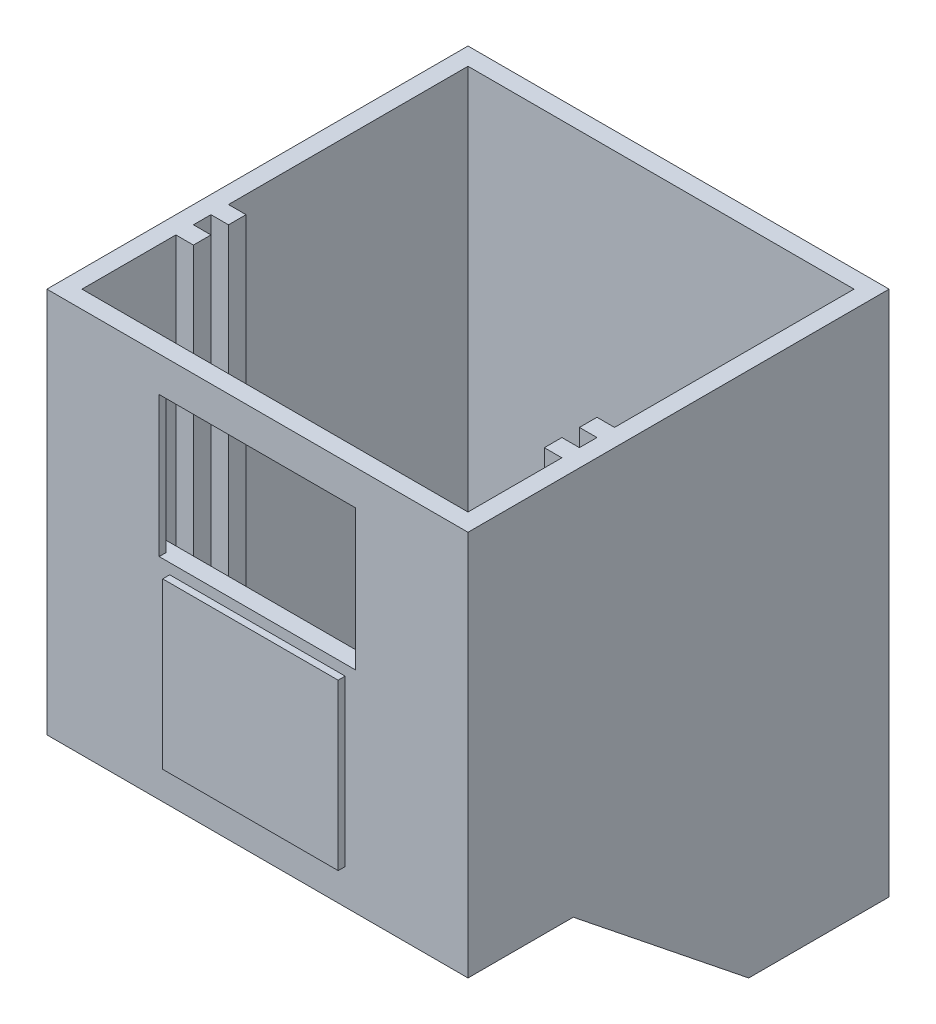
SolidWorks part; units mm, degrees
ref_plane "Front Plane" through (0, 0, 0) normal (0, 0, 1) x (1, 0, 0)
ref_plane "Top Plane" through (0, 0, 0) normal (0, 1, 0) x (1, 0, 0)
ref_plane "Right Plane" through (0, 0, 0) normal (1, 0, 0) x (0, 0, -1)
sketch "Sketch1" plane through (0, 0, 0) normal (0, 1, 0) x (1, 0, 0)
  line L1 (-60, -60) -> (60, -60)
  line L2 (-60, -60) -> (-60, 60)
  line L3 (-60, 60) -> (60, 60)
  line L4 (60, -60) -> (60, 60)
  line L5 (-60, -60) -> (60, 60) construction
  line L6 (-60, 60) -> (60, -60) construction
  point P0 (0, 0)
  dimension "D1" = 120
  dimension "D2" = 120
extrude "Boss-Extrude1" add sketch "Sketch1" along normal blind 150
sketch "Sketch13" plane through (60, 0, 0) normal (1, 0, 0) x (0, 0, -1)
  line L0 (-30, 40) -> (20, 0)
  line L1 (-60, 0) -> (-30, 0)
  line L2 (-60, 0) -> (-60, 40)
  line L3 (-60, 40) -> (-30, 40)
  line L5 (-60, 0) -> (60, 0) construction
  line L8 (-30, 0) -> (20, 0)
  dimension "D1" = 30
  dimension "D2" = 40
  dimension "D3" = 40
extrude "Cut-Extrude7" cut sketch "Sketch13" against normal up to next
shell "Shell1" thickness 5 removed face at (0, 150, 0)
sketch "Sketch3" plane through (0, 0, 0) normal (0, -1, 0) x (1, 0, 0)
  line L0 (60, -20) -> (60, -60) construction
  line L4 (-60, 60) -> (60, 60) construction
  circle A0 centre (0, 50) radius 2.5
  circle A1 centre (-5, 40) radius 1.5
  circle A2 centre (5, 40) radius 1.5
  dimension "D3" = 5
  dimension "D4" = 3
  dimension "D5" = 10
  dimension "D6" = 55
  dimension "D7" = 10
  dimension "D8" = 20
  dimension "D1" = 50
  dimension "D2" = 60
extrude "Cut-Extrude2" cut sketch "Sketch3" against normal up to next
sketch "Sketch5" plane through (0, 0, 60) normal (0, 0, 1) x (1, 0, 0)
  line L0 (60, 150) -> (60, 40) construction
  line L1 (-25, 50) -> (25, 50)
  line L2 (-25, 50) -> (-25, 97)
  line L3 (-25, 97) -> (25, 97)
  line L4 (25, 50) -> (25, 97)
  line L5 (-25, 50) -> (25, 97) construction
  line L6 (-25, 97) -> (25, 50) construction
  line L7 (-60, 150) -> (60, 150) construction
  point P0 (0, 73.5)
  dimension "D1" = 50
  dimension "D2" = 47
  dimension "D3" = 60
  dimension "D4" = 76.5
extrude "Boss-Extrude3" add sketch "Sketch5" along normal blind 2
sketch "Sketch8" plane through (0, 0, 60) normal (0, 0, 1) x (1, 0, 0)
  line L0 (-60, 150) -> (-60, 40) construction
  line L1 (-28, 100) -> (28, 100)
  line L2 (-28, 100) -> (-28, 140)
  line L3 (-28, 140) -> (28, 140)
  line L4 (28, 100) -> (28, 140)
  line L5 (-28, 100) -> (28, 140) construction
  line L6 (-28, 140) -> (28, 100) construction
  line L7 (-60, 150) -> (60, 150) construction
  point P0 (0, 120)
  dimension "D1" = 56
  dimension "D2" = 40
  dimension "D3" = 60
  dimension "D4" = 50
extrude "Cut-Extrude3" cut sketch "Sketch8" against normal up to next
sketch "Sketch9" plane through (0, 0, 55) normal (0, 0, -1) x (-1, 0, 0)
  line L17 (28, 100) -> (-28, 100) construction
  line L18 (-28, 140) -> (-35.5, 140)
  line L19 (-28, 140) -> (-28, 100)
  line L20 (-28, 100) -> (-35.5, 100)
  line L21 (-35.5, 140) -> (-35.5, 100)
  line L22 (-28, 100) -> (-28, 140) construction
  line L23 (0, 100) -> (0, 140) construction
  line L24 (-28, 140) -> (28, 140) construction
  line L25 (28, 100) -> (35.5, 100)
  line L26 (35.5, 140) -> (35.5, 100)
  line L27 (28, 140) -> (35.5, 140)
  line L28 (28, 140) -> (28, 100)
  dimension "D1" = 40
  dimension "D2" = 0
  dimension "D3" = 7.5
  dimension "D4" = 0
extrude "Cut-Extrude4" cut sketch "Sketch9" against normal offset from surface (3 mm away) 2 up to face at (0, 120, 60)
sketch "Sketch10" plane through (0, 0, 62) normal (0, 0, 1) x (1, 0, 0)
  line L0 (-25, 50) -> (25, 50) construction
  line L1 (-22.5, 94.5) -> (22.5, 94.5)
  line L2 (-22.5, 94.5) -> (-22.5, 52.5)
  line L3 (-22.5, 52.5) -> (22.5, 52.5)
  line L4 (22.5, 94.5) -> (22.5, 52.5)
  line L5 (25, 50) -> (25, 97) construction
  dimension "D1" = 45
  dimension "D2" = 42
  dimension "D3" = 2.5
  dimension "D4" = 2.5
extrude "Cut-Extrude5" cut sketch "Sketch10" against normal up to surface (7 mm away) from offset 4 up to face at (0, 120, 55) offset against normal yes
sketch "Sketch16" plane through (0, 150, 0) normal (0, 1, 0) x (1, 0, 0)
  line L0 (55, -55) -> (55, 55) construction
  line L1 (55, -13.2461) -> (50, -13.2461)
  line L2 (55, -13.2461) -> (55, -18.2461)
  line L3 (55, -18.2461) -> (50, -18.2461)
  line L4 (50, -13.2461) -> (50, -18.2461)
  line L5 (55, 21.7539) -> (55, -28.2461) construction
  line L6 (55, -23.2461) -> (50, -23.2461)
  line L7 (55, -23.2461) -> (55, -28.2461)
  line L8 (55, -28.2461) -> (50, -28.2461)
  line L9 (50, -23.2461) -> (50, -28.2461)
  line L11 (-55, -28.2461) -> (55, -28.2461) construction
  dimension "D1" = 5
  dimension "D2" = 5
  dimension "D3" = 5
  dimension "D4" = 5
  dimension "D5" = 5
  dimension "D6" = 0
extrude "Boss-Extrude5" add sketch "Sketch16" against normal up to next
mirror "Mirror1" about plane through (0, 0, 0) normal (1, 0, 0) of "Boss-Extrude5"
sketch "Sketch17" plane through (0, 9.7561, -7.8049) normal (0, -0.7809, 0.6247) x (1, 0, 0)
  line L0 (-60, -15.6174) -> (60, -15.6174) construction
  line L1 (0, 14.3826) -> (-2, 14.3826)
  line L2 (-2, 14.3826) -> (-2, 39.3025)
  line L3 (0, 14.3826) -> (2, 14.3826)
  line L4 (2, 14.3826) -> (2, 39.3025)
  line L5 (60, -15.6174) -> (60, 48.4139) construction
  line L6 (-1.4142, 12.9684) -> (-19.0352, 30.5894)
  line L7 (1.4142, 15.7968) -> (-16.2068, 33.4178)
  line L8 (0, 14.3826) -> (1.4142, 15.7968)
  line L9 (0, 12.3826) -> (-24.9199, 12.3826)
  line L10 (0, 16.3826) -> (-24.9199, 16.3826)
  line L11 (0, 14.3826) -> (0, 16.3826)
  line L12 (1.4142, 12.9684) -> (-16.2068, -4.6526)
  line L13 (-1.4142, 15.7968) -> (-19.0352, -1.8242)
  line L14 (0, 14.3826) -> (-1.4142, 15.7968)
  line L15 (2, 14.3826) -> (2, -10.5372)
  line L16 (-2, 14.3826) -> (-2, -10.5372)
  line L17 (0, 14.3826) -> (-2, 14.3826)
  line L18 (1.4142, 15.7968) -> (19.0352, -1.8242)
  line L19 (-1.4142, 12.9684) -> (16.2068, -4.6526)
  line L20 (0, 14.3826) -> (-1.4142, 12.9684)
  line L21 (0, 16.3826) -> (24.9199, 16.3826)
  line L22 (0, 12.3826) -> (24.9199, 12.3826)
  line L23 (0, 14.3826) -> (0, 12.3826)
  line L24 (-1.4142, 15.7968) -> (16.2068, 33.4178)
  line L25 (1.4142, 12.9684) -> (19.0352, 30.5894)
  line L26 (0, 14.3826) -> (1.4142, 12.9684)
  circle A0 centre (0, 14.3826) radius 25
  circle A1 centre (0, 14.3826) radius 22.5
  circle A2 centre (0, 14.3826) radius 20
  circle A3 centre (0, 14.3826) radius 17.5
  circle A4 centre (0, 14.3826) radius 5
  circle A5 centre (0, 14.3826) radius 15
  circle A6 centre (0, 14.3826) radius 12.5
  circle A7 centre (0, 14.3826) radius 10
  circle A8 centre (0, 14.3826) radius 7.5
  circle A9 centre (0, 14.3826) radius 2.5
  dimension "D1" = 50
  dimension "D2" = 30
  dimension "D3" = 45
  dimension "D4" = 40
  dimension "D5" = 35
  dimension "D6" = 10
  dimension "D11" = 30
  dimension "D12" = 25
  dimension "D13" = 20
  dimension "D14" = 15
  dimension "D15" = 5
  dimension "D7" = 4
  dimension "D8" = 2
  dimension "D9" = 60
  dimension "D10" = 8
extrude "Cut-Extrude8" cut sketch "Sketch17" against normal blind 5 contours A1 L2 A0 L7 | A1 L6 A0 L10 | A1 L9 A0 L13 | A1 L12 A0 L16 | A1 L15 A0 L19 | A1 L18 A0 L22 | A1 L21 A0 L25 | A1 L24 A0 L4 | A3 L2 A2 L7 | A3 L6 A2 L10 | A3 L9 A2 L13 | A3 L12 A2 L16 | A3 L15 A2 L19 | A3 L18 A2 L22 | A3 L21 A2 L25 | A3 L24 A2 L4 | A6 L6 A5 L10 | A6 L2 A5 L7 | A6 L24 A5 L4 | A6 L21 A5 L25 | A6 L18 A5 L22 | A6 L15 A5 L19 | A6 L12 A5 L16 | A6 L9 A5 L13 | A8 L12 A7 L16 | A8 L15 A7 L19 | A8 L18 A7 L22 | A8 L21 A7 L25 | A8 L24 A7 L4 | A8 L2 A7 L7 | A8 L6 A7 L10 | A8 L9 A7 L13 | A9 region at (-3.3885, 23.8512, 9.814) region at (-8.1806, 20.8576, 6.072) region at (-8.1806, 16.6241, 0.7801) region at (-3.3885, 13.6305, -2.9619) region at (3.3885, 23.8512, 9.814) region at (8.1806, 20.8576, 6.072) region at (8.1806, 16.6241, 0.7801) region at (3.3885, 13.6305, -2.9619) region at (-5.2312, 26.6303, 13.2879) region at (-12.6293, 22.0088, 7.511) region at (-12.6293, 15.4729, -0.6589) region at (-5.2312, 10.8514, -6.4358) region at (5.2312, 26.6303, 13.2879) region at (12.6293, 22.0088, 7.511) region at (12.6293, 15.4729, -0.6589) region at (5.2312, 10.8514, -6.4358) region at (-7.0923, 29.437, 16.7963) region at (-17.1222, 23.1714, 8.9642) region at (-17.1222, 14.3103, -2.1121) region at (-7.0923, 8.0447, -9.9442) region at (7.0923, 29.437, 16.7963) region at (17.1222, 23.1714, 8.9642) region at (17.1222, 14.3103, -2.1121) region at (7.0923, 8.0447, -9.9442) region at (-8.9558, 32.2475, 20.3093) region at (-21.6212, 24.3355, 10.4193) region at (-21.6212, 13.1462, -3.5672) region at (-8.9558, 5.2342, -13.4572) region at (8.9558, 32.2475, 20.3093) region at (21.6212, 24.3355, 10.4193) region at (21.6212, 13.1462, -3.5672) region at (8.9558, 5.2342, -13.4572)
